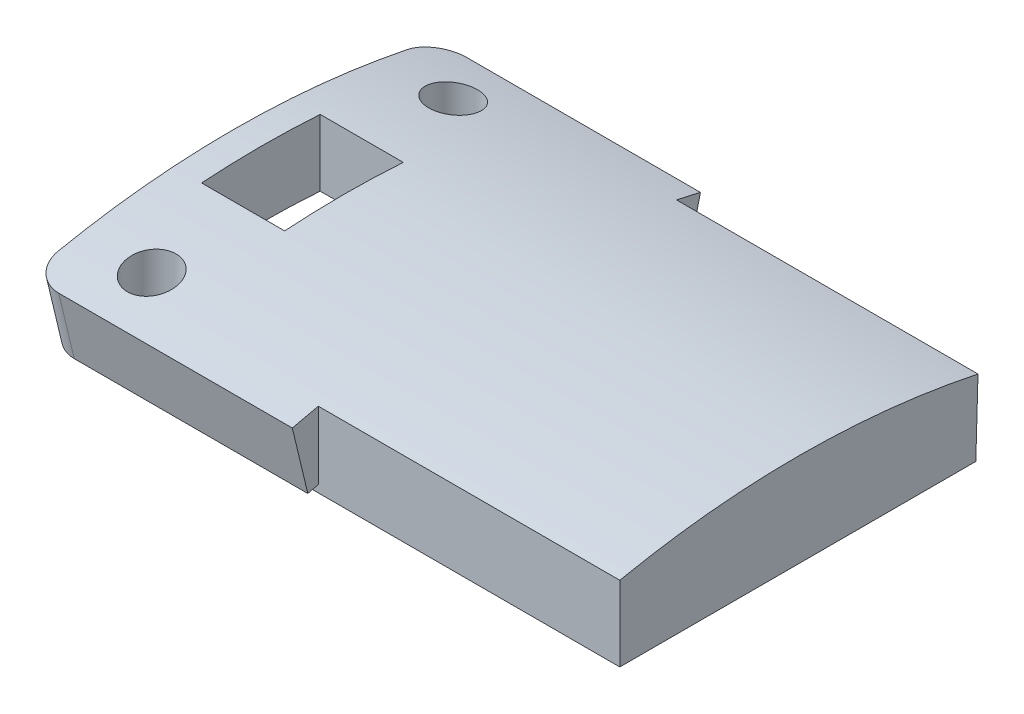
SolidWorks part; units mm, degrees
ref_plane "Front Plane" through (0, 0, 0) normal (0, 0, 1) x (1, 0, 0)
ref_plane "Top Plane" through (0, 0, 0) normal (0, 1, 0) x (1, 0, 0)
ref_plane "Right Plane" through (0, 0, 0) normal (1, 0, 0) x (0, 0, -1)
sketch "Sketch1" plane through (0, 0, 0) normal (0, 0, 1) x (1, 0, 0)
  line L0 (21.581, -73.66) -> (-66.7143, -73.66) construction
  line L1 (-11.1125, -5.588) -> (11.1125, -5.588)
  line L2 (11.1125, -5.588) -> (11.1125, 0)
  line L3 (11.1125, 0) -> (-11.1125, 0)
  line L4 (-11.1125, 0) -> (-11.1125, -5.588)
  dimension "D1" = 73.66
  dimension "D2" = 5.588
  dimension "D3" = 22.225
revolve "Revolve1" add sketch "Sketch1" angle 27 mid plane about L0
sketch "Sketch2" plane through (0, 0, 0) normal (0, 1, 0) x (1, 0, 0)
  line L0 (-11.1125, 17.1956) -> (-11.1125, -17.1956) construction
  line L1 (-1.7313, -5) -> (-8.7312, -5)
  line L2 (-1.7313, -5) -> (-1.7313, 5)
  line L3 (-1.7313, 5) -> (-8.7312, 5)
  line L4 (-8.7312, -5) -> (-8.7312, 5)
  line L5 (-1.7313, -5) -> (-8.7312, 5) construction
  line L6 (-1.7313, 5) -> (-8.7312, -5) construction
  line L7 (11.1125, -17.1956) -> (11.1125, 17.1956) construction
  line L8 (-11.1125, 17.1956) -> (-11.1125, -17.1956)
  line L9 (11.1125, -17.1956) -> (11.1125, 17.1956)
  line L10 (-11.1125, 0) -> (11.1125, 0) construction
  circle A1 centre (-5.2313, 12.7) radius 2.05
  circle A2 centre (-5.2313, -12.7) radius 2.05
  point P0 (-5.2313, 0)
  dimension "D6" = 4.1
  dimension "D1" = 10
  dimension "D2" = 7
  dimension "D4" = 2.3813
  dimension "D7" = 12.7
extrude "Cut-Extrude1" cut sketch "Sketch2" against normal through all contours L4 L1 L2 L3 | A1 | A2 region at (-5.2313, 0, 0)
ref_plane "Plane1" through (3.3487, 0, 0) normal (-1, 0, 0) x (0, 0, 1)
shell "Shell2" [suppressed] thickness 1.905
sketch "Sketch5" [suppressed] plane through (9.2075, 0, 0) normal (-1, 0, 0) x (0, 0, 1)
  line L2 (3.383, -0.1219) -> (3.383, -5.7264)
  line L6 (8.8642, -6.548) -> (10.3118, -1.1454)
  line L7 (8.8642, -6.548) -> (10.3118, -1.1454)
  line L8 (3.383, -0.1219) -> (3.383, -5.7264)
  arc A2 (8.8642, -6.548) -> (3.383, -5.7264) centre (0, -46.99) ccw
  arc A3 (8.8642, -6.548) -> (3.383, -5.7264) centre (0, -46.99) ccw
  arc A6 (10.3118, -1.1454) -> (3.383, -0.1219) centre (0, -46.99) ccw
  arc A7 (10.3118, -1.1454) -> (3.383, -0.1219) centre (0, -46.99) ccw
  dimension "D1" = 0
extrude "Cut-Extrude2" [suppressed] cut sketch "Sketch5" against normal through all
fillet "Fillet1" [suppressed] radius 2.54
fillet "Fillet2" radius 2.54 2 edges at (-11.1125, -4.752, -16.5433) (-11.1125, -4.752, 16.5433)
sketch "Sketch8" plane through (11.1125, 0, 0) normal (1, 0, 0) x (0, 0, -1)
  line L2 (-15, -7.874) -> (15, -7.874)
  line L5 (-15, -7.874) -> (-15, -1.5435)
  line L6 (15, -7.874) -> (15.1846, -1.5821)
  arc A0 (17.1956, -2.0352) -> (-17.1956, -2.0352) centre (0, -73.66) ccw construction
  arc A1 (15.1846, -1.5821) -> (-15, -1.5435) centre (0, -73.66) ccw
  point P0 (0, -7.874)
  dimension "D1" = 30
  dimension "D2" = 7.874
extrude "Boss-Extrude2" add sketch "Sketch8" along normal blind 25.4 and the other way blind 1.27
hole_wizard "#24 (0.152) Diameter Hole1" positions "Sketch9" profile "Sketch10" hole size "#24" standard "ANSI Inch"
sketch "Sketch9" plane through (0, -7.874, 0) normal (0, -1, 0) x (-1, 0, 0)
  line L2 (1.7313, -5) -> (1.7313, 5) construction
  point P0 (-32.2687, 11.5)
  point P2 (-32.2687, -11.5)
  dimension "D1" = 23
  dimension "D2" = 11.5
  dimension "D3" = 34
sketch "Sketch10" plane through (32.2687, -7.874, -11.5) normal (1, 0, 0) x (0, 0, -1)
  line L0 (0, 0) -> (0, 4.5599)
  line L1 (0, 4.5599) -> (1.9304, 3.4)
  line L2 (1.9304, 3.4) -> (1.9304, 0)
  line L5 (1.9304, 0) -> (0, 0)
  line L10 (0, 4.5599) -> (-1.9304, 3.4) construction
  line L11 (0, -6.35) -> (0, 107.95) construction
  dimension "Hole Dia." = 3.8608
  dimension "Hole Depth" = 3.4
  dimension "Drill Angle" = 118
sketch "Sketch12" plane through (9.8425, 0, 0) normal (-1, 0, 0) x (0, 0, 1)
  circle A0 centre (-23.333, -17.3422) radius 9
  dimension "D1" = 18
extrude "Cut-Extrude3" [suppressed] cut sketch "Sketch12" against normal blind 24
sketch "Sketch13" [suppressed] plane through (33.8425, 0, 0) normal (-1, 0, 0) x (0, 0, 1)
  circle A0 centre (-23.333, -17.3422) radius 9
  arc A1 (-19.6767, -9.1184) -> (-31.734, -14.1138) centre (-23.333, -17.3422) ccw construction
extrude "Boss-Extrude3" [suppressed] add sketch "Sketch13" against normal up to surface (2.67 mm away) up to face at (36.5125, -4.3277, -0.0467)
fillet "Fillet3" [suppressed] radius 2.54
sketch "Sketch14" [suppressed] plane through (9.8425, 0, 0) normal (-1, 0, 0) x (0, 0, 1)
  line L0 (-40.4766, -12.1178) -> (-37.0776, -17.2858)
  line L1 (-15, -7.874) -> (-17.2354, -2.0448)
  arc A0 (-13.4235, -1.2334) -> (-40.4766, -12.1178) centre (0, -73.66) ccw construction
  arc A1 (-40.4766, -12.1178) -> (-17.2354, -2.0448) centre (0, -73.66) cw
  arc A2 (-37.0776, -17.2858) -> (-31.734, -14.1138) centre (0, -73.66) cw
  arc A3 (-31.734, -14.1138) -> (-37.0776, -17.2858) centre (0, -73.66) ccw construction
  arc A4 (-31.734, -14.1138) -> (-19.6767, -9.1184) centre (-23.333, -17.3422) cw
  arc A5 (-19.6767, -9.1184) -> (-31.734, -14.1138) centre (-23.333, -17.3422) ccw construction
  arc A6 (-19.6767, -9.1184) -> (-15, -7.874) centre (0, -73.66) cw
  arc A7 (-15, -7.874) -> (-19.6767, -9.1184) centre (0, -73.66) ccw construction
extrude "Boss-Extrude4" [suppressed] add sketch "Sketch14" along normal blind 20
sketch "Sketch16" [suppressed] plane through (33.8425, 0, 0) normal (-1, 0, 0) x (0, 0, 1)
  line L0 (-27.4395, -19.0436) -> (-24.4441, -26.2734)
  line L1 (-19.2265, -15.6408) -> (-16.2311, -22.8706)
  line L2 (-23.333, -17.3422) -> (0, -73.66) construction
  arc A0 (-19.2265, -15.6408) -> (-27.4395, -19.0436) centre (-23.333, -17.3422) ccw
  circle A1 centre (-23.333, -17.3422) radius 9 construction
  arc A2 (-16.2311, -22.8706) -> (-24.4441, -26.2734) centre (-23.333, -17.3422) cw
  circle A3 centre (0, -73.66) radius 73.66 construction
  arc A4 (-17.2354, -2.0448) -> (-40.4766, -12.1178) centre (0, -73.66) ccw construction
  dimension "D1" = 8.89
extrude "Cut-Extrude4" [suppressed] cut sketch "Sketch16" against normal through all
fillet "Fillet5" [suppressed] radius 0.254
equation "\"Mid_Coupler_ID\"= 3.7"
equation "\"Thiccness\"= 5.5mm"
equation "\"Bracket_Angle\"= 27"
equation "\"D1@Revolve1\"=\"Bracket_Angle\""
equation "\"Cam_Slot_Width\"= 10mm"
equation "\"Cam_Slot_Length\"= 7mm"
equation "\"D1@Sketch2\"=\"Cam_Slot_Width\""
equation "\"D2@Sketch2\"=\"Cam_Slot_Length\""
equation "\"Screw_Angle\"= 12.5deg"
equation "\"M3_Insert_OD\"= 4.1mm"
equation "\"Length\"= ( 7 / 8 ) * 1in"
equation "\"D3@Sketch1\"=\"Length\""
equation "\"Mid_Tube_Length\"= 1in"
equation "\"Bodytube_OD\" = 6.17in"
equation "\"Bodytube_ID\" = 5.998in"
equation "\"Camera_Cutout_Width\"=10mm"
equation "\"Camera_Cutout_Height\"=7mm"
equation "\"Fwd_Tube_Length\" = 38.5in"
equation "\"BKHD_Screw_Diam\"= 3.5mm"
equation "\"Fwd_BKHD_From_Top\" = 18in"
equation "\"Shear_Screw_Diameter\" = 0.086in"
equation "\"Shear_Screw_Coupler_Location\" = 4.5in"
equation "\"Motor_OD\" = 4in"
equation "\"Mid_Coupler_Length\" = 13in"
equation "\"Aft_Section_Length\"= 36in"
equation "\"AB_Coupler_OD_Length\"= 1in"
equation "\"AB_Coupling_Section_Length\"= 0.375in"
equation "\"AB_Coupler_Length\"= \"AB_Coupler_OD_Length\" + \"AB_Coupling_Section_Length\" * 2"
equation "\"Cutout_Angle\" = 80"
equation "\"AB_Paddle_Height\" = 0.375in"
equation "\"AB_Coupler_Num_Screws\"= 4"
equation "\"AB_BKHD_Thickness\" = 0.375in"
equation "\"AB_Mount_From_Bottom\" = 23.175in"
equation "\"Num_Cutouts\" = 3"
equation "\"AB_Coupler_OD\"= 6.17in"
equation "\"AB_Coupler_ID\"= 5.75in"
equation "\"AB_Coupler_Surface_Diameter\"= 5.998in"
equation "\"AB_Coupling_Screw_Diameter\"= 0.15748in"
equation "\"AB_Central_Bushing_Length\" = .4724in"
equation "\"Lead_Screw_Dist\" = 3.4in"
equation "\"Lead_Screw_Diam\" = 0.386in"
equation "\"Lead_Screw_Length\" = (\"Mid_Coupler_Length\" + 2*0.375in + 2*.75in)"
equation "\"Paddle_Pin_Offset\" = .25in"
equation "\"Paddle_Pin_Radius\" = 2.25in"
equation "\"SS_Paddle_Pin_Radius\" = 2.25*0.66in"
equation "\"Paddle_Gear_OD\" = 3.2in"
equation "\"Drive_Gear_OD\" = 1.7in"
equation "\"Fin_Thickness\"= .118in"
equation "\"Guiderail_Cutout_Diameter\"= 1.5in"
equation "\"DB9_Hole_Dist\" = 25mm"
equation "\"DB9_Relief_Width\" = 0.47in"
equation "\"DB9_Relief_Hole_Offset\" = 0.09in"
equation "\"Airbrakes_Wire_Hole_Dia\" = .25in"
equation "\"Airbrakes_Wire_Hole_Dist\" = 1.1in"
equation "\"Servo_Gear_Offset\" = 0.5in"
equation "\"FWD_Shear_Screw_Dist\" = 1.5in"
equation "\"Camera_Screw_Dia\" = 0.216535"
equation "\"Camera_Hole_Angle\" = atn ( 2 / 3 * tan ( 12.5deg ) )"
equation "\"Coupler_OD\" = 5.998"
equation "\"Coupler_ID\" = 5.8"
equation "\"D1@Sketch3\"=\"Camera_Hole_Angle\"/2"
equation "\"D2@Sketch3\"=2*\"Thiccness\""
equation "\"D3@Sketch3\"=\"M3_Insert_OD\"/2"
